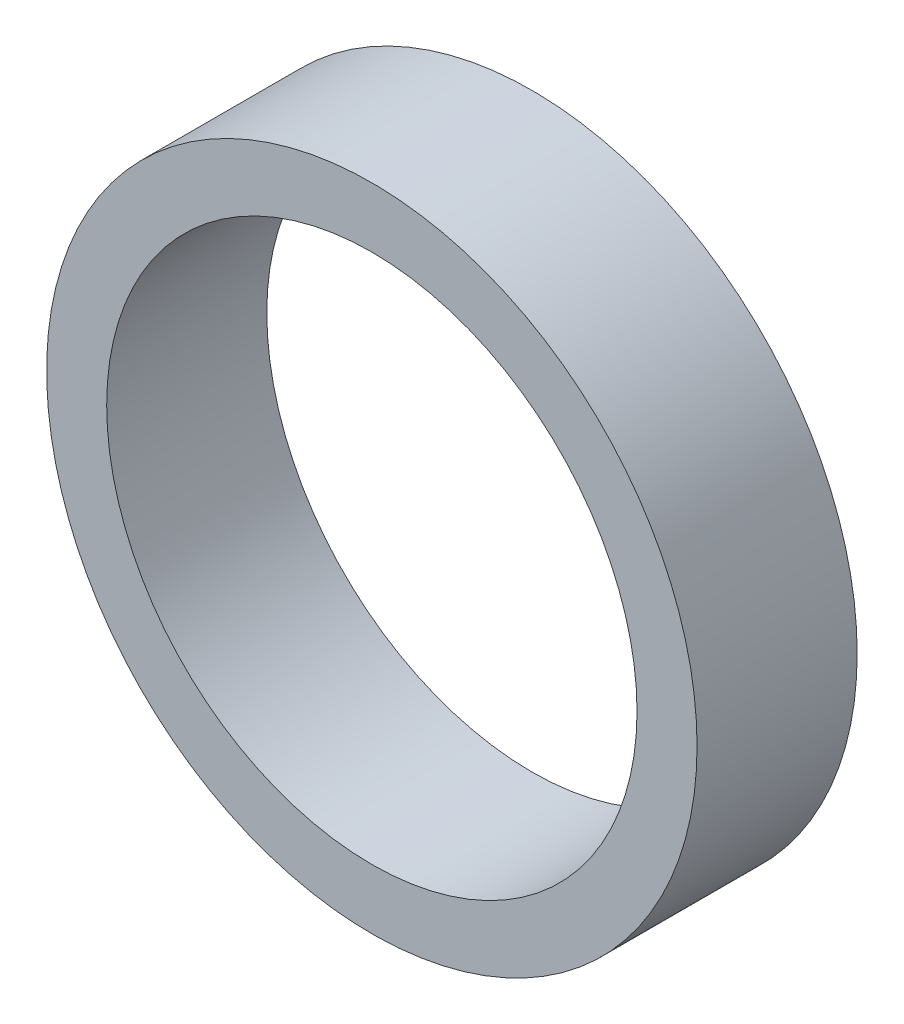
SolidWorks part; units mm, degrees
ref_plane "Front Plane" through (0, 0, 0) normal (0, 0, 1) x (1, 0, 0)
ref_plane "Top Plane" through (0, 0, 0) normal (0, 1, 0) x (1, 0, 0)
ref_plane "Right Plane" through (0, 0, 0) normal (1, 0, 0) x (0, 0, -1)
sketch "Sketch1" plane through (0, 0, 0) normal (0, 0, 1) x (1, 0, 0)
  circle A0 centre (0, 0) radius 2.65
  circle A1 centre (0, 0) radius 3.25
  dimension "D1" = 5.3
  dimension "D2" = 0.6
extrude "Boss-Extrude1" add sketch "Sketch1" along normal blind 1.6
